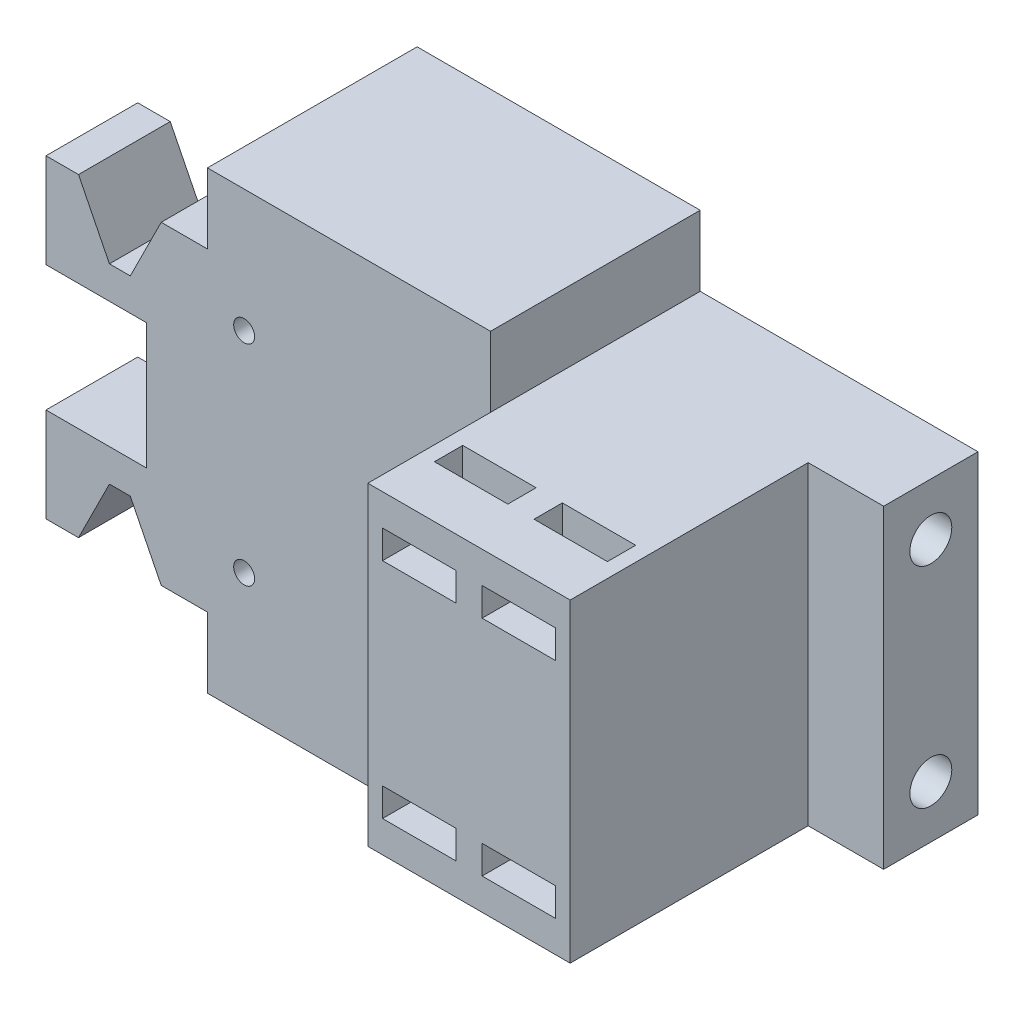
SolidWorks part; units mm, degrees
ref_plane "Front Plane" through (0, 0, 0) normal (0, 0, 1) x (1, 0, 0)
ref_plane "Top Plane" through (0, 0, 0) normal (0, 1, 0) x (1, 0, 0)
ref_plane "Right Plane" through (0, 0, 0) normal (1, 0, 0) x (0, 0, -1)
sketch "BackFace-Sketch1" plane through (0, 0, 0) normal (0, 0, 1) x (1, 0, 0)
  line L0 (0, 0) -> (0, 9)
  line L1 (0, 9) -> (9.6, 9)
  line L2 (9.6, 9) -> (9.6, 21)
  line L3 (9.6, 21) -> (0, 21)
  line L4 (0, 21) -> (0, 30)
  line L5 (0, 30) -> (3.1, 30)
  line L6 (3.1, 30) -> (6.05, 24.096)
  line L7 (6.05, 24.096) -> (8.04, 24.096)
  line L8 (8.04, 24.096) -> (10.99, 30)
  line L9 (10.99, 30) -> (15.4, 30)
  line L10 (68.9, 30) -> (68.9, 0)
  line L11 (68.9, 0) -> (42.4, 0)
  line L12 (10.99, 0) -> (8.04, 5.904)
  line L13 (8.04, 5.904) -> (6.05, 5.904)
  line L14 (6.05, 5.904) -> (3.1, 0)
  line L15 (3.1, 0) -> (0, 0)
  line L16 (15.4, 0) -> (15.4, -6.7)
  line L17 (15.4, -6.7) -> (42.4, -6.7)
  line L18 (42.4, -6.7) -> (42.4, 0)
  line L19 (15.4, 30) -> (15.4, 36.7)
  line L20 (15.4, 36.7) -> (42.4, 36.7)
  line L21 (42.4, 36.7) -> (42.4, 30)
  line L22 (42.4, 30) -> (68.9, 30)
  line L23 (15.4, 0) -> (10.99, 0)
  point P13 (4.8, 9)
  point P17 (4.575, 2.952)
  point P18 (7.045, 24.096)
  point P19 (7.045, 5.904)
  dimension "D1" = 3.1
  dimension "D2" = 9
  dimension "D4" = 6.6
  dimension "D5" = 1.99
  dimension "D7" = 30
  dimension "D8" = 9.6
  dimension "D6" = 2.95
  dimension "D9" = 27
  dimension "D10" = 43.4
  dimension "D11" = 4.41
  dimension "D3" = 26.5
  dimension "D12" = 59.3
extrude "Boss-Extrude1" add sketch "BackFace-Sketch1" along normal blind 20
sketch "EarKnotch-Sketch2" plane through (0, 0, 0) normal (0, 0, -1) x (-1, 0, 0)
  line L0 (-15.4, 30) -> (-10.99, 30) construction
  line L1 (0, 30) -> (-7.1, 30)
  line L2 (0, 30) -> (0, 0)
  line L3 (0, 0) -> (-7.1, 0)
  line L4 (-7.1, 30) -> (-7.1, 0)
  line L5 (-42.4, 0) -> (-68.9, 0) construction
  line L8 (0, 30) -> (0, 21) construction
  dimension "D1" = 7.1
extrude "EarKnotch-Cut-Extrude1" cut sketch "EarKnotch-Sketch2" against normal blind 11.25
sketch "TopHoles-Sketch3" plane through (0, 0, 0) normal (-1, 0, 0) x (0, 0, 1)
  line L0 (20, 30) -> (20, 21) construction
  line L1 (20, 30) -> (11.25, 30) construction
  line L2 (20, 0) -> (11.25, 0) construction
  circle A0 centre (15.5, 25.5) radius 2.3
  circle A1 centre (15.5, 4.5) radius 2.3
  dimension "D4" = 4.6
  dimension "D1" = 4.5
  dimension "D2" = 4.5
  dimension "D3" = 4.5
extrude "TopHoles-Cut-Extrude2" cut sketch "TopHoles-Sketch3" against normal blind 4
sketch "FrontHoles-Sketch1" plane through (0, 0, 0) normal (0, 0, -1) x (-1, 0, 0)
  line L0 (-68.9, 0) -> (-68.9, 30) construction
  line L1 (-15.4, 30) -> (-10.99, 30) construction
  line L2 (-42.4, 0) -> (-68.9, 0) construction
  circle A0 centre (-45.25, 25) radius 2
  circle A1 centre (-45.25, 5) radius 2
  circle A2 centre (-33.25, 25) radius 2
  circle A3 centre (-33.25, 5) radius 2
  dimension "D2" = 4
  dimension "D1" = 23.65
  dimension "D3" = 12
  dimension "D4" = 5
  dimension "D5" = 5
extrude "FrontHoles-Cut-Extrude1" cut sketch "FrontHoles-Sketch1" against normal blind 7
sketch "RearMountingHoles-Sketch2" plane through (0, 0, 20) normal (0, 0, 1) x (1, 0, 0)
  line L0 (42.4, 0) -> (68.9, 0) construction
  line L1 (15.4, 30) -> (10.99, 30) construction
  line L2 (15.4, 36.7) -> (15.4, 30) construction
  circle A0 centre (18.9, 25) radius 1
  circle A1 centre (18.9, 5) radius 1
  circle A2 centre (38.9, 25) radius 1
  circle A3 centre (38.9, 5) radius 1
  dimension "D6" = 2
  dimension "D2" = 20
  dimension "D3" = 5
  dimension "D1" = 20
  dimension "D5" = 3.5
extrude "RearMountingHoles-Cut-Extrude2" cut sketch "RearMountingHoles-Sketch2" against normal through all
sketch "RearMountingHolesBoreSketch4" plane through (0, 0, 0) normal (0, 0, -1) x (-1, 0, 0)
  circle A0 centre (-38.9, 25) radius 2
  circle A1 centre (-18.9, 25) radius 2
  circle A2 centre (-38.9, 5) radius 2
  circle A3 centre (-18.9, 5) radius 2
  dimension "D1" = 4
extrude "RearMountingHolesBoreCut-Extrude2" cut sketch "RearMountingHolesBoreSketch4" against normal blind 4
sketch "BlockUnderRail-Sketch1" plane through (0, 0, 20) normal (0, 0, 1) x (1, 0, 0)
  line L0 (68.9, 0) -> (68.9, 30) construction
  line L1 (42.4, 30) -> (68.9, 30)
  line L2 (42.4, 30) -> (42.4, 0)
  line L3 (42.4, 0) -> (68.9, 0)
  line L4 (68.9, 30) -> (68.9, 0)
  line L5 (68.9, 30) -> (42.4, 30) construction
  line L6 (42.4, 30) -> (42.4, 36.7) construction
extrude "BlockUnderRail-Boss-Extrude2" add sketch "BlockUnderRail-Sketch1" along normal blind 11.7
sketch "RearRibbonHoles-Sketch2" plane through (0, 0, 31.7) normal (0, 0, 1) x (1, 0, 0)
  line L0 (15.4, 36.7) -> (15.4, 30) construction
  line L1 (43.8, 27) -> (50.8, 27)
  line L2 (43.8, 27) -> (43.8, 24.3)
  line L3 (43.8, 24.3) -> (50.8, 24.3)
  line L4 (50.8, 27) -> (50.8, 24.3)
  line L5 (53.3, 27) -> (60.3, 27)
  line L6 (53.3, 27) -> (53.3, 24.3)
  line L7 (53.3, 24.3) -> (60.3, 24.3)
  line L8 (60.3, 27) -> (60.3, 24.3)
  line L9 (43.8, 5.7) -> (50.8, 5.7)
  line L10 (43.8, 5.7) -> (43.8, 3)
  line L11 (43.8, 3) -> (50.8, 3)
  line L12 (50.8, 5.7) -> (50.8, 3)
  line L13 (53.3, 5.7) -> (60.3, 5.7)
  line L14 (53.3, 5.7) -> (53.3, 3)
  line L15 (53.3, 3) -> (60.3, 3)
  line L16 (60.3, 5.7) -> (60.3, 3)
  line L20 (42.4, 0) -> (68.9, 0) construction
  line L21 (68.9, 30) -> (42.4, 30) construction
  dimension "D3" = 2.7
  dimension "D4" = 7
  dimension "D5" = 2.5
  dimension "D2" = 3
  dimension "D1" = 3
  dimension "D6" = 28.4
extrude "RearRibbonHoles-Cut-Extrude1" cut sketch "RearRibbonHoles-Sketch2" against normal blind 7.65
sketch "LeftRibbonHoles-Sketch3" plane through (0, 0, 0) normal (0, -1, 0) x (1, 0, 0)
  line L0 (43.8, 24.05) -> (50.8, 24.05) construction
  line L1 (43.8, 26.75) -> (50.8, 26.75)
  line L2 (43.8, 26.75) -> (43.8, 24.05)
  line L3 (43.8, 24.05) -> (50.8, 24.05)
  line L4 (50.8, 26.75) -> (50.8, 24.05)
  line L5 (53.3, 26.75) -> (60.3, 26.75)
  line L6 (53.3, 26.75) -> (53.3, 24.05)
  line L7 (53.3, 24.05) -> (60.3, 24.05)
  line L8 (60.3, 26.75) -> (60.3, 24.05)
  line L9 (43.8, 24.05) -> (43.8, 31.7) construction
  line L10 (50.8, 24.05) -> (50.8, 31.7) construction
  line L11 (53.3, 24.05) -> (53.3, 31.7) construction
  line L12 (60.3, 24.05) -> (60.3, 31.7) construction
  dimension "D1" = 2.7
sketch "RightRibbonHoles-Sketch4" plane through (0, 30, 0) normal (0, 1, 0) x (1, 0, 0)
  line L0 (60.3, -24.05) -> (53.3, -24.05) construction
  line L9 (50.8, -24.05) -> (43.8, -24.05) construction
  line L10 (43.8, -24.05) -> (43.8, -31.7) construction
  line L11 (53.3, -24.05) -> (53.3, -31.7) construction
  line L13 (60.3, -24.05) -> (60.3, -31.7) construction
  line L14 (43.8, -24.05) -> (50.8, -24.05)
  line L15 (43.8, -24.05) -> (43.8, -26.75)
  line L16 (43.8, -26.75) -> (50.8, -26.75)
  line L17 (50.8, -24.05) -> (50.8, -26.75)
  line L18 (53.3, -24.05) -> (60.3, -24.05)
  line L19 (53.3, -24.05) -> (53.3, -26.75)
  line L20 (53.3, -26.75) -> (60.3, -26.75)
  line L21 (60.3, -24.05) -> (60.3, -26.75)
  line L22 (50.8, -24.05) -> (50.8, -31.7) construction
  line L23 (50.8, -24.05) -> (43.8, -24.05) construction
  line L26 (55.51, -26.7) -> (33.1572, -26.7) construction
  line L27 (50.99, -28.35) -> (33.1572, -28.35) construction
  line L28 (42.4, -20) -> (15.4, -20) construction
  dimension "D1" = 2.7
  dimension "D2" = 8.35
extrude "RightRibbonHoles-Cut-Extrude2" cut sketch "RightRibbonHoles-Sketch4" against normal blind 5.7
extrude "LeftRibbonHoles-Cut-Extrude2" cut sketch "LeftRibbonHoles-Sketch3" against normal blind 5.7
sketch "BottomClampMountingHolesSketch3" plane through (68.9, 0, 0) normal (1, 0, 0) x (0, 0, -1)
  line L0 (-20, 30) -> (0, 30) construction
  line L1 (-20, 0) -> (0, 0) construction
  line L4 (0, 0) -> (0, 30) construction
  circle A0 centre (-4.5, 25) radius 2
  circle A1 centre (-4.5, 5) radius 2
  dimension "D3" = 5
  dimension "D1" = 4
  dimension "D2" = 5
  dimension "D4" = 4.5
extrude "BottomClampMountHolesCut-Extrude1" cut sketch "BottomClampMountingHolesSketch3" against normal blind 4.1
fillet "RibbonHoleFillet1" radius 2.7 1 edges at (56.8, 5.7, 24.05)
fillet "RibbonHoleFillet2" radius 2.7 1 edges at (47.3, 5.7, 24.05)
fillet "RibbonHoleFillet3" radius 2.7 1 edges at (56.8, 24.3, 24.05)
fillet "RibbonHoleFillet4" radius 2.7 1 edges at (47.3, 24.3, 24.05)
sketch "ExcessEndSketch1" plane through (0, 0, 31.7) normal (0, 0, 1) x (1, 0, 0)
  line L0 (42.4, 0) -> (68.9, 0) construction
  line L1 (68.9, 30) -> (61.7, 30)
  line L2 (68.9, 30) -> (68.9, 0)
  line L3 (68.9, 0) -> (61.7, 0)
  line L4 (61.7, 30) -> (61.7, 0)
  line L5 (60.3, 27) -> (60.3, 24.3) construction
  dimension "D1" = 1.4
extrude "ExcessEndCut-Extrude1" cut sketch "ExcessEndSketch1" against normal blind 22.7
equation "\"CarrierWidth\"= \"LinearGBWidthWithBumpers\" - 2mm"
equation "\"LinearGBWidth\"= 27mm'Spec"
equation "\"D10@BackFace-Sketch1\"=\"CarrierWidth\""
equation "\"LinearGBWidthWithBumpers\"= 45.4mm"
equation "\"LinearGBMountHolesXDistance\"= 20mm'Spec"
equation "\"LinearGBMountHolesYDistance\"= 20mm'Spec"
equation "\"D1@RearMountingHoles-Sketch2\"=\"LinearGBMountHolesXDistance\""
equation "\"D2@RearMountingHoles-Sketch2\"=\"LinearGBMountHolesYDistance\""
equation "\"D5@RearMountingHoles-Sketch2\"= ( \"LinearGBWidth\" - \"LinearGBMountHolesYDistance\" ) / 2"
equation "\"CarrierRibbonHoleWidth\"= 7mm"
equation "\"CarrierRibbonHoleHeight\"= 2.7mm"
equation "\"CarrierRibbonHoleDistance\"= 2.5mm'Equals 2.5. Must equal distance created by GABRiserBossOffset"
equation "\"CarrierRibbonHoleOffsetFromSide\"= 3.0mm"
equation "\"CarrierDepth\"= 20mm"
equation "\"D1@Boss-Extrude1\"=\"CarrierDepth\""
equation "\"D3@RearRibbonHoles-Sketch2\" = \"CarrierRibbonHoleHeight\""
equation "\"D4@RearRibbonHoles-Sketch2\" = \"CarrierRibbonHoleWidth\""
equation "\"D5@RearRibbonHoles-Sketch2\" = \"CarrierRibbonHoleDistance\""
equation "\"D9@BackFace-Sketch1\"=\"LinearGBWidth\""
equation "\"D2@RearRibbonHoles-Sketch2\"=\"CarrierRibbonHoleOffsetFromSide\""
equation "\"D1@RearRibbonHoles-Sketch2\"=\"CarrierRibbonHoleOffsetFromSide\""
equation "\"D1@RightRibbonHoles-Cut-Extrude2\" = \"CarrierRibbonHoleOffsetFromSide\" + \"CarrierRibbonHoleHeight\""
equation "\"LinearRailHeight\"= 8mm'Spec"
equation "\"LinearGBDepth\"= 10mm'Spec"
equation "\"D1@BlockUnderRail-Boss-Extrude2\"=\"MiddleOfGBAndLinearRail\" +  \"CarrierRibbonHoleHeight\""
equation "\"D1@LeftRibbonHoles-Cut-Extrude2\" = \"CarrierRibbonHoleOffsetFromSide\" + \"CarrierRibbonHoleHeight\""
equation "\"D1@RightRibbonHoles-Sketch4\"=\"CarrierRibbonHoleHeight\""
equation "\"D1@RearRibbonHoles-Cut-Extrude1\"=\"MiddleOfGBAndLinearRail\" - \"CarrierRibbonHoleHeight\"/2mm"
equation "\"D1@LeftRibbonHoles-Sketch3\"=\"CarrierRibbonHoleHeight\""
equation "\"MiddleOfGBAndLinearRail\"= \"LinearGBDepth\" / 2 + \"LinearRailHeight\" / 2"
equation "\"CarrierUpperBodyLength\"= \"CarrierBodyLength\" - \"LinearGBWidth\" - \"CarrierLowerBodyLength\""
equation "\"CarrierLowerBodyLength\"= \"CarrierRibbonHoleWidth\" * 2 + \"CarrierRibbonHoleDistance\" + 5mm * 2"
equation "\"D3@BackFace-Sketch1\"=\"CarrierLowerBodyLength\""
equation "\"D11@BackFace-Sketch1\"=\"CarrierUpperBodyLength\""
equation "\"CarrierBodyLength\"= 59.3mm - 1.39mm'From the 100 1.39 accounts for the little slant"
equation "\"M3HeatInsertHoleDiamter\"=4"
equation "\"LM8UUHeight\"= 24mm'Spec"
equation "\"ZAxisLeadScrewLength\"= 200mm"
equation "\"LegHeight\"= 70mm'Space needed for PSU/Stepper/Electronics"
equation "\"V1 BottomOfLowerRail\"= \"LegHeight\""
equation "\"StepperShaftLength\"= 24mm'Pulley will be attached to the end"
equation "\"V2 ToBedAtTopOfZAxis\"= \"V1 BottomOfLowerRail\" - \"LowerEnclosureThickness\" + \"StepperShaftLength\" + \"ZAxisLeadScrewLength\" - \"LM8UUHeight\" / 2'Equals 277"
equation "\"HotEndToTopOfXAxisGB\"= 71.68487mm'Equals 71.68487. Measured after installed onto X-Axis linear rail guide block"
equation "\"TopOfGBToBottomOfLinearRail\"= \"LinearGBWidth\" / 2 + \"LinearRailWidth\" / 2'Equals 19.5"
equation "\"V5 ToBottomOfXAxisLinearRail\"= \"V4 ToTopOfBuildPlate/HotEndTip\" + \"HotEndToTopOfXAxisGB\" - \"TopOfGBToBottomOfLinearRail\"'Equals 352.18487"
equation "\"LinearRailWidth\"= 12mm'Spec"
equation "\"V6 ToMiddleOfYAxisGantryBlock\"= \"V5 ToBottomOfXAxisLinearRail\" - \"GABHeight\" / 2'Equals 334.18487"
equation "\"LowerEnclosureThickness\"= 5mm"
equation "\"V4 ToTopOfBuildPlate/HotEndTip\"= \"V2 ToBedAtTopOfZAxis\" + \"BedToBuildPlateStandoffLength\" + \"BuildPlateHeight\""
equation "\"BedToBuildPlateStandoffLength\"= 15mm"
equation "\"BuildPlateHeight\"= 8mm'Spec"
equation "\"GABLowerHeight\"= 4mm"
equation "\"GABMidWallHeight\"= 28mm'Must equal 28 or changes alignment"
equation "\"GABUpperHeight\"= 4mm"
equation "\"GABHeight\"= \"GABLowerHeight\" + \"GABMidWallHeight\" + \"GABUpperHeight\""
equation "\"V5.1 ToBottomXAxisGBMountingHole\"= \"V4 ToTopOfBuildPlate/HotEndTip\" + \"HotEndToTopOfXAxisGB\" - \"LinearGBWidth\" / 2 - \"LinearGBMountHolesYDistance\" / 2"
equation "\"D1@BottomClampMountingHolesSketch3\"=\"M3HeatInsertHoleDiamter\""
equation "\"M3HeatInsertHoleDepth\"= 4.1mm'Spec"
equation "\"D1@BottomClampMountHolesCut-Extrude1\"=\"M3HeatInsertHoleDepth\""
equation "\"D1@RibbonHoleFillet1\" = \"CarrierRibbonHoleHeight\""
equation "\"D1@RibbonHoleFillet2\"=\"CarrierRibbonHoleHeight\""
equation "\"D1@RibbonHoleFillet3\"=\"CarrierRibbonHoleHeight\""
equation "\"D1@RibbonHoleFillet4\"=\"CarrierRibbonHoleHeight\""
equation "\"XXX\"= \"TopOfGBToBottomOfLinearRail\" + \"DistanceFromXAxisLinearRailBottomAndTopGantryPulley\""
equation "\"20TGT2PulleyWidth\"= 8.7mm'The STL of the Pulley in the diagram is a bit larger"
equation "\"GABMidShortRiserHeight\"= \"GABMidWallHeight\" / 2 - \"20TGT2PulleyWidth\"'Equals 5.3"
equation "\"DistanceFromXAxisLinearRailBottomAndTopGantryPulley\"= \"GABUpperHeight\" + \"GABMidShortRiserHeight\" - \"GABRiserBossOffset\"'Equals 8.9"
equation "\"GABRiserBossOffset\"= 0.4mm'A;igns Pulleys inside edges to be 2.5mm (.5mm apart top to bottom)"
